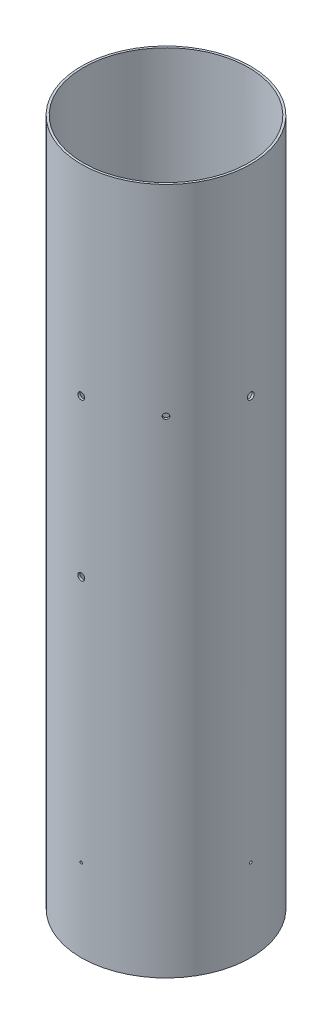
SolidWorks part; units mm, degrees
material "C-Glass Fiber"
ref_plane "Front Plane" through (0, 0, 0) normal (0, 0, 1) x (1, 0, 0)
ref_plane "Top Plane" through (0, 0, 0) normal (0, 1, 0) x (1, 0, 0)
ref_plane "Right Plane" through (0, 0, 0) normal (1, 0, 0) x (0, 0, -1)
sketch "Sketch2" plane through (0, 0, 0) normal (0, 1, 0) x (1, 0, 0)
  circle A0 centre (0, 0) radius 76.3651
  circle A1 centre (0, 0) radius 78.359
  dimension "D1" = 152.7302
  dimension "D2" = 156.718
extrude "Boss-Extrude1" add sketch "Sketch2" along normal blind 635
sketch "Sketch3" plane through (0, 0, 0) normal (0, 0, 1) x (1, 0, 0)
  circle A0 centre (0, 76.2) radius 1.1906
  dimension "D2" = 2.3813
  dimension "D1" = 76.2
extrude "Cut-Extrude1" cut sketch "Sketch3" against normal through all both and the other way through all
pattern_circular "CirPattern1" count 4 over 360 about axis through (0, 635, 0) along (0, 1, 0) of "Cut-Extrude1"
sketch "Sketch4" plane through (0, 0, 0) normal (0, 0, 1) x (1, 0, 0)
  circle A0 centre (0, 449.5038) radius 3.175
  dimension "D2" = 6.35
  dimension "D1" = 449.5038
extrude "Cut-Extrude2" cut sketch "Sketch4" against normal through all both and the other way through all
pattern_circular "CirPattern2" count 4 over 360 about axis through (0, 635, 0) along (0, 1, 0) of "Cut-Extrude2"
ref_plane "Plane1" through (55.4082, 0, 55.4082) normal (0.7071, 0, 0.7071) x (0, -1, 0)
sketch "Sketch5" plane through (55.4082, 0, 55.4082) normal (0.7071, 0, 0.7071) x (0, -1, 0)
  circle A0 centre (-449.5038, 0) radius 2.5019
  dimension "D1" = 5.0038
  dimension "D2" = 449.5038
extrude "Cut-Extrude3" cut sketch "Sketch5" against normal up to surface and the other way through all up to face at (-76.3025, 448.7766, 3.0906)
sketch "Sketch6" plane through (0, 0, 0) normal (0, 0, 1) x (1, 0, 0)
  circle A0 centre (0, 304.8) radius 3.175
  dimension "D2" = 304.8
extrude "Cut-Extrude4" cut sketch "Sketch6" against normal through all both and the other way through all
sketch "Sketch7" plane through (0, 635, 0) normal (0, 1, 0) x (1, 0, 0)
  line L0 (0, 0) -> (78.359, 0)
  circle A0 centre (0, 0) radius 78.359 construction
ref_plane "Plane2" through (0, 449.58, 0) normal (0, 1, 0) x (1, 0, 0)
sketch "Sketch8" plane through (0, 449.58, 0) normal (0, 1, 0) x (1, 0, 0)
  line L0 (0, 0) -> (78.359, 0) construction
  line L1 (0, 0) -> (78.359, 0)
  line L2 (0, 0) -> (53.8815, -53.8815) construction
  line L3 (0, 0) -> (0, 76.3651) construction
  circle A0 centre (0, 0) radius 76.3651 construction
  dimension "D1" = 76.2
  dimension "D2" = 45
ref_plane "Plane3" through (0, 304.8, 0) normal (0, 1, 0) x (1, 0, 0)
sketch "Sketch9" plane through (0, 304.8, 0) normal (0, 1, 0) x (1, 0, 0)
  line L0 (0, 0) -> (78.359, 0) construction
  line L1 (0, 0) -> (78.359, 0)
  line L2 (0, 0) -> (0, 76.3651) construction
  line L3 (0, 0) -> (0, -76.3651) construction
  circle A0 centre (0, 0) radius 76.3651 construction
ref_plane "Plane4" through (0, 76.2, 0) normal (0, 1, 0) x (1, 0, 0)
sketch "Sketch10" plane through (0, 76.2, 0) normal (0, 1, 0) x (1, 0, 0)
  line L0 (0, 0) -> (78.359, 0) construction
  line L1 (0, 0) -> (0, 76.3651) construction
  line L2 (0, 0) -> (78.359, 0)
  line L3 (0, 0) -> (0, 76.3651) construction
equation "\"Shear Pin Dia\"= 3 / 32"
equation "\"Shear Pin Offset\"= 3"
equation "\"D1@Sketch3\"=\"Shear Pin Offset\""
equation "\"D2@Sketch3\"=\"Shear Pin Dia\""
equation "\"Bulkhead Screw Dia\"= 1 / 4"
equation "\"Bulkhead Screw Offset\"= 17.697"
equation "\"D1@Sketch4\"=\"Bulkhead Screw Offset\""
equation "\"D2@Sketch4\"=\"Bulkhead Screw Dia\""
equation "\"Rail Button Offset\"= 17.697"
equation "\"Rail Button Dia\"= 0.197"
equation "\"D1@Sketch5\"=\"Rail Button Dia\""
equation "\"Vent Hole Dia\"= 0.25"
equation "\"Vent Hole Offset\"= 12"
equation "\"D2@Sketch6\"=\"Vent Hole Offset\""
